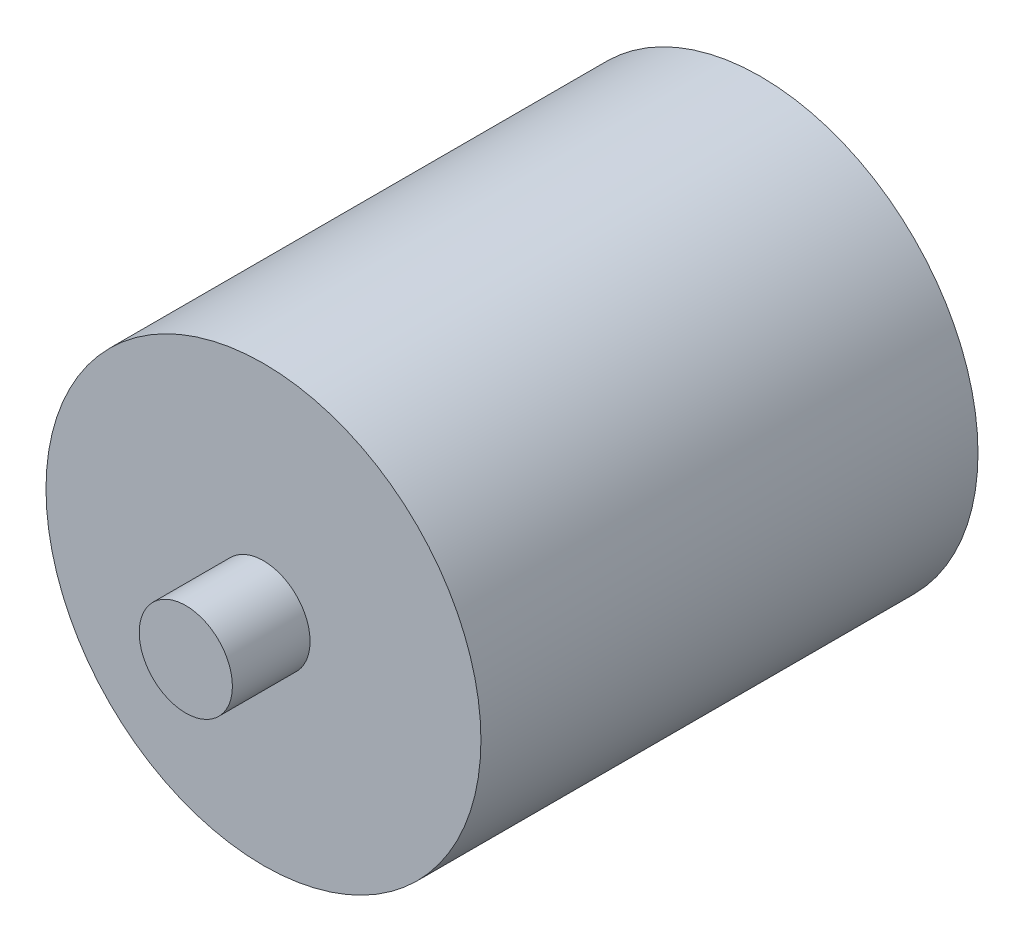
SolidWorks part; units mm, degrees
material "Stainless Steel (ferritic)"
ref_plane "Front Plane" through (0, 0, 0) normal (0, 0, 1) x (1, 0, 0)
ref_plane "Top Plane" through (0, 0, 0) normal (0, 1, 0) x (1, 0, 0)
ref_plane "Right Plane" through (0, 0, 0) normal (1, 0, 0) x (0, 0, -1)
sketch "Sketch1" plane through (0, 0, 0) normal (0, 0, 1) x (1, 0, 0)
  line L0 (0, 14) -> (0, -14) construction
  line L1 (-14, 0) -> (14, 0) construction
  circle A0 centre (0, 0) radius 14
  circle A1 centre (-9.5, 0) radius 1.5
  circle A2 centre (0, 8) radius 1.5
  circle A3 centre (0, -8) radius 1.5
  circle A4 centre (9.5, 0) radius 1.5
  dimension "D1" = 28
  dimension "D4" = 19
  dimension "D2" = 3
  dimension "D3" = 3
  dimension "D5" = 16
extrude "Boss-Extrude1" add sketch "Sketch1" along normal blind 32 contours A0 A3 A2 A1 A4 | A1 | A2 | A4 | A3 region at (0, 0, 0) region at (-9.5, 0, 0) region at (0, 8, 0) region at (0, -8, 0) region at (9.5, 0, 0)
extrude "Cut-Extrude1" cut sketch "Sketch1<3>" along normal blind 5 contours A2 | A1 | A3 | A4 region at (-9.5, 0, 0) region at (0, 8, 0) region at (0, -8, 0) region at (9.5, 0, 0)
sketch "Sketch1<3>" plane through (0, 0, 0) normal (0, 0, 1) x (1, 0, 0) same geometry as "Sketch1"
sketch "Sketch2" plane through (0, 0, 32) normal (0, 0, 1) x (1, 0, 0)
  circle A0 centre (0, 0) radius 3
  dimension "D1" = 6
extrude "Boss-Extrude2" add sketch "Sketch2" along normal blind 5
